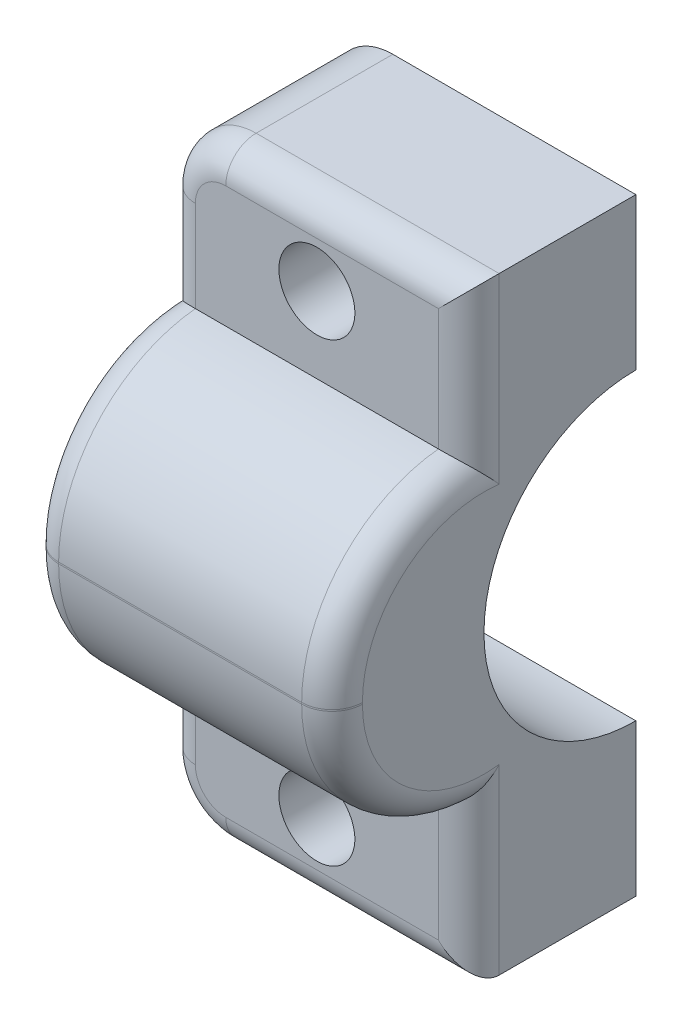
SolidWorks part; units mm, degrees
ref_plane "Front Plane" through (0, 0, 0) normal (0, 0, 1) x (1, 0, 0)
ref_plane "Top Plane" through (0, 0, 0) normal (0, 1, 0) x (1, 0, 0)
ref_plane "Right Plane" through (0, 0, 0) normal (1, 0, 0) x (0, 0, -1)
sketch "Sketch3" plane through (0, 0, 0) normal (0, 0, 1) x (1, 0, 0)
  line L0 (-22, -21.5) -> (-65, -21.5) construction
  line L1 (-65, -43) -> (65, -43) construction
  line L2 (-65, -43) -> (-65, 43) construction
  line L3 (-65, 43) -> (65, 43) construction
  line L4 (65, -43) -> (65, 43) construction
  line L5 (-65, -43) -> (65, 43) construction
  line L6 (-65, 43) -> (65, -43) construction
  line L7 (-65, -43) -> (-22, -43) construction
  line L8 (-65, -43) -> (-65, 0) construction
  line L9 (-65, 0) -> (-22, 0) construction
  line L10 (-22, -43) -> (-22, 0) construction
  circle A0 centre (-25, -3) radius 2.75
  circle A1 centre (-62, -3) radius 2.75
  circle A2 centre (-25, -40) radius 2.75
  circle A3 centre (-62, -40) radius 2.75
  point P0 (0, 0)
  dimension "D5" = 3
  dimension "D6" = 37
  dimension "D1" = 130
  dimension "D2" = 86
  dimension "D3" = 43
  dimension "D4" = 43
  dimension "D7" = 3
  dimension "D8" = 3
  dimension "D9" = 3
  dimension "D10" = 3
extrude "Boss-Extrude1" add sketch "Sketch3" along normal blind 6
sketch "Sketch4" plane through (0, 0, 0) normal (0, 0, 1) x (1, 0, 0)
  line L1 (-22, -43) -> (-65, -43)
  line L2 (-22, -43) -> (-22, 43)
  line L3 (-22, 43) -> (-65, 43)
  line L4 (-65, -43) -> (-65, 43)
extrude "Boss-Extrude2" add sketch "Sketch4" against normal blind 2.5
mirror "Mirror4" about plane through (0, 0, 0) normal (0, 1, 0) of "Boss-Extrude1"
sketch "Sketch5" plane through (0, 0, 6) normal (0, 0, 1) x (1, 0, 0)
  circle A0 centre (-25, 40) radius 2.75
extrude "Boss-Extrude3" add sketch "Sketch5" along normal blind 10
pattern_linear "LPattern1" count 2 spacing 37 along (-1, 0, 0) of "Boss-Extrude3"
pattern_linear "LPattern2" count 2 spacing 37 along (0, -1, 0) of "LPattern1"
sketch "Sketch6" plane through (0, 0, 0) normal (0, 0, 1) x (1, 0, 0)
  line L1 (-22, -43) -> (65, -43)
  line L2 (-22, -43) -> (-22, 43)
  line L3 (-22, 43) -> (65, 43)
  line L4 (65, -43) -> (65, 43)
extrude "Boss-Extrude4" add sketch "Sketch6" against normal blind 2.5
sketch "Sketch7" plane through (0, 0, 0) normal (0, 0, 1) x (1, 0, 0)
  line L0 (-22, -32.544) -> (-6, -32.544) construction
  line L1 (-22, -43) -> (-22, 0) construction
  line L2 (0, 0) -> (0, -43) construction
  line L3 (-65, -43) -> (65, -43) construction
  line L4 (0, -43) -> (-6, -32.544) construction
  line L5 (-6, -32.544) -> (0, -32.544) construction
  dimension "D1" = 16
  dimension "D2" = 6
ref_plane "Plane1" through (-6, 0, 0) normal (1, 0, 0) x (0, 0, -1)
sketch "Sketch11" plane through (-6, 0, 0) normal (1, 0, 0) x (0, 0, -1)
  line L0 (0, -43) -> (-40, -43)
  line L1 (-40, -43) -> (-40, -39)
  line L2 (0, -43) -> (0, -18)
  line L3 (0, -43) -> (0, 43) construction
  line L4 (-40, -39) -> (0, -18)
  dimension "D1" = 40
extrude "Boss-Extrude5" add sketch "Sketch11" along normal blind 2 and the other way blind 2
sketch "Sketch12" plane through (-8, 0, 0) normal (-1, 0, 0) x (0, 0, 1)
  line L0 (0, -43) -> (0, -36) construction
  line L1 (40, -43) -> (0, -43) construction
  line L2 (0, 43) -> (0, -43) construction
  line L3 (6, -37.25) -> (6, -36) construction
  line L8 (6, -42.75) -> (6, -37.25) construction
  line L9 (6, -37.25) -> (0, -37.25) construction
  line L10 (6, -36) -> (0, -36) construction
  line L12 (6, -36) -> (10, -36)
  line L13 (6, -36) -> (6, -28)
  line L14 (6, -28) -> (10, -28)
  line L15 (10, -36) -> (10, -28)
  dimension "D1" = 7
  dimension "D2" = 8
  dimension "D3" = 4
sketch "Sketch13" plane through (0, 0, 0) normal (0, 0, 1) x (1, 0, 0)
  line L0 (-22.25, -40) -> (-8, -40) construction
  line L1 (-8, -43) -> (-8, -36) construction
  circle A0 centre (-25, -40) radius 2.75 construction
  circle A1 centre (-25, -40) radius 2.75 construction
  dimension "D1" = 14.25
extrude "Cut-Extrude1" cut sketch "Sketch12" against normal blind 4
sketch "Sketch14" plane through (0, -43, 0) normal (0, -1, 0) x (1, 0, 0)
  line L0 (-6, -23.375) -> (-6, 23.375) construction
  line L1 (-8, 40) -> (-4, 40) construction
  line L2 (-6, 37) -> (-6, 13.6) construction
  circle A0 centre (-6, 37) radius 0.85
  circle A2 centre (-6, 13.6) radius 0.85
  dimension "D1" = 3
  dimension "D2" = 23.4
extrude "Cut-Extrude2" cut sketch "Sketch14" against normal blind 4.5
pattern_linear "LPattern3" count 2 spacing 46.5 along (1, 0, 0) of "Boss-Extrude5", "Cut-Extrude2"
sketch "Sketch16" plane through (0, -43, 0) normal (0, -1, 0) x (1, 0, 0)
  line L0 (40.5, 13.6) -> (40.5, -2.5)
  line L1 (-65, -2.5) -> (65, -2.5) construction
sketch "Sketch17" plane through (0, 0, 0) normal (0, 0, 1) x (1, 0, 0)
  line L0 (42.5, -43) -> (42.5, -41) construction
  line L1 (42.5, -43) -> (42.5, -18) construction
  line L2 (61.9, -8.8) -> (63.9, -8.8) construction
  line L3 (42.5, -41) -> (61.9, -41) construction
  line L4 (42.5, -41) -> (42.5, 23.4) construction
  line L5 (42.5, 23.4) -> (61.9, 23.4) construction
  line L6 (61.9, -41) -> (61.9, 23.4) construction
  line L7 (52.2, 23.4) -> (52.2, 25.4) construction
  line L8 (42.5, -8.8) -> (40.5, -8.8) construction
  line L9 (42.5, -41) -> (42.5, -43)
  line L10 (42.5, -43) -> (63.9, -43)
  line L11 (42.5, -43) -> (65, -43) construction
  line L12 (63.9, -43) -> (63.9, 25.4)
  line L13 (63.9, 25.4) -> (40.5, 25.4)
  line L14 (40.5, 25.4) -> (40.5, -18)
  line L15 (38.5, -18) -> (42.5, -18) construction
  line L16 (40.5, -18) -> (42.5, -18)
  line L17 (42.5, -18) -> (42.5, 23.4)
  line L18 (42.5, 23.4) -> (61.9, 23.4)
  line L19 (61.9, 23.4) -> (61.9, -41)
  line L20 (61.9, -41) -> (42.5, -41)
  dimension "D1" = 19.4
  dimension "D2" = 64.4
extrude "Boss-Extrude6" add sketch "Sketch17" along normal blind 35
sketch "Sketch18" plane through (0, -18, 0) normal (0, -1, 0) x (1, 0, 0)
  line L1 (42.5, 35) -> (40.5, 35)
  line L2 (42.5, 35) -> (42.5, 0)
  line L3 (42.5, 0) -> (40.5, 0)
  line L4 (40.5, 35) -> (40.5, 0)
extrude "Boss-Extrude7" add sketch "Sketch18" along normal blind 18.5
sketch "Sketch19" plane through (0, 0, 0) normal (0, 0, 1) x (1, 0, 0)
  line L1 (0, 0) -> (32.48, 0)
  line L2 (0, 0) -> (0, 17.04)
  line L3 (0, 17.04) -> (32.48, 17.04)
  line L4 (32.48, 0) -> (32.48, 17.04)
  dimension "D1" = 32.48
  dimension "D2" = 17.04
extrude "Boss-Extrude8" add sketch "Sketch19" along normal blind 10
sketch "Sketch20" plane through (0, 0, 10) normal (0, 0, 1) x (1, 0, 0)
  line L0 (0, 17.04) -> (0, 0) construction
  line L1 (2, 2) -> (10.16, 2)
  line L2 (2, 2) -> (2, 15.04)
  line L3 (2, 15.04) -> (10.16, 15.04)
  line L4 (10.16, 2) -> (10.16, 15.04)
  line L5 (0, 0) -> (32.48, 0) construction
  line L6 (32.48, 17.04) -> (0, 17.04) construction
  line L7 (32.48, 0) -> (32.48, 17.04) construction
  line L8 (12.16, 15.04) -> (20.32, 15.04)
  line L9 (12.16, 15.04) -> (12.16, 2)
  line L10 (12.16, 2) -> (20.32, 2)
  line L11 (20.32, 15.04) -> (20.32, 2)
  line L12 (22.32, 15.04) -> (30.48, 15.04)
  line L13 (22.32, 15.04) -> (22.32, 2)
  line L14 (22.32, 2) -> (30.48, 2)
  line L15 (30.48, 15.04) -> (30.48, 2)
  line L16 (0, 17.04) -> (32.48, 17.04) construction
  dimension "D1" = 2
  dimension "D2" = 2
  dimension "D3" = 2
  dimension "D4" = 2
  dimension "D5" = 2
  dimension "D6" = 2
  dimension "D7" = 8.16
  dimension "D8" = 8.16
  dimension "D9" = 8.16
  dimension "D10" = 13.04
  dimension "D11" = 13.04
  dimension "D12" = 13.04
  dimension "D13" = 2
extrude "Cut-Extrude3" cut sketch "Sketch20" against normal blind 10
sketch "Sketch21" plane through (0, 0, 0) normal (0, 0, 1) x (1, 0, 0)
  line L0 (65, -43) -> (65, 43) construction
  line L1 (63.9, -43) -> (65, -43)
  line L2 (63.9, -43) -> (63.9, 43)
  line L3 (63.9, 43) -> (65, 43)
  line L4 (65, -43) -> (65, 43)
extrude "Cut-Extrude4" cut sketch "Sketch21" against normal blind 10
fillet "Fillet2" radius 2 4 edges at (-65, 43, -1.25) (-65, -43, -1.25) (63.9, 25.4, 17.5) (63.9, -43, 16.25)
fillet "Fillet4" radius 20 1 edges at (63.9, 43, -1.25)
sketch "Sketch23" plane through (0, 0, -2.5) normal (0, 0, -1) x (-1, 0, 0)
  line L0 (0, 0) -> (65, 0) construction
  line L1 (65, 41) -> (65, -41) construction
  line L2 (65, 0) -> (105, 0) construction
  line L3 (105, 10) -> (105, -10) construction
  line L4 (105, -10) -> (105, -16) construction
  line L5 (65, 41) -> (65, -41) construction
  line L6 (95.4802, -10) -> (105, -10)
  line L7 (105, -10) -> (110, -10)
  line L8 (110, -10) -> (110, 10)
  line L9 (95.4802, 10) -> (105, 10)
  line L10 (65, -41) -> (65, 41)
  line L11 (105, 10) -> (110, 10)
  spline S0 degree 2 poles (95.4802, -10) (68.263, -8.8623) (65, -41) knots 0 0 0 1 1 1
  spline S1 degree 2 poles (95.4802, 10) (68.263, 8.8623) (65, 41) knots 0 0 0 1 1 1
  point P9 (105, 0)
  point P18 (110, 0)
  dimension "D1" = 20
extrude "Boss-Extrude9" add sketch "Sketch23" against normal blind 2.5
sketch "Sketch24" plane through (0, 0, 0) normal (0, 0, 1) x (1, 0, 0)
  line L0 (-95.4802, -10) -> (-105, -10) construction
  line L1 (-110, 10) -> (-100, 10)
  line L2 (-110, 10) -> (-110, -10)
  line L3 (-110, -10) -> (-100, -10)
  line L4 (-100, 10) -> (-100, -10)
  line L5 (-105, 3.4723) -> (-65, 3.4723) construction
  line L6 (-105, 10) -> (-105, -10) construction
  line L7 (-65, -41) -> (-65, 41) construction
  dimension "D1" = 10
extrude "Boss-Extrude10" add sketch "Sketch24" along normal blind 30
sketch "Sketch25" plane through (-110, 0, 0) normal (-1, 0, 0) x (0, 0, 1)
  line L0 (30, 10) -> (-2.5, 10) construction
  line L3 (30, 10) -> (30, -10) construction
  line L4 (20, 5) -> (20, 10) construction
  circle A0 centre (20, 0) radius 5
  dimension "D1" = 10
  dimension "D2" = 10
extrude "Cut-Extrude6" cut sketch "Sketch25" against normal blind 30
fillet "Fillet6" radius 10 1 edges at (-100, 0, 0)
fillet "Fillet8" radius 2 2 edges at (-110, 10, 13.75) (-110, -10, 13.75)
sketch "Sketch27" plane through (0, 0, -2.5) normal (0, 0, -1) x (-1, 0, 0)
  line L0 (110, 5) -> (110, 10) construction
  line L1 (110, 10) -> (90, 10)
  line L2 (110, 10) -> (110, -10.1307)
  line L3 (110, -10.1307) -> (90, -10.1307)
  line L4 (90, 10) -> (90, -10.1307)
extrude "Cut-Extrude7" cut sketch "Sketch27" against normal blind 22.5
sketch "Sketch28" plane through (-90, 0, 0) normal (-1, 0, 0) x (0, 0, 1)
  line L1 (-12.2204, 55.5192) -> (66.9065, 55.5192)
  line L2 (-12.2204, 55.5192) -> (-12.2204, -56.8134)
  line L3 (-12.2204, -56.8134) -> (66.9065, -56.8134)
  line L4 (66.9065, 55.5192) -> (66.9065, -56.8134)
extrude "Cut-Extrude10" cut sketch "Sketch28" against normal blind 210.5 and the other way blind 7.5
sketch "Sketch29" plane through (0, 0, 20) normal (0, 0, -1) x (-1, 0, 0)
  line L0 (105, 5) -> (105, 10) construction
  line L1 (110, 5) -> (100, 5) construction
  line L2 (108, 10) -> (100, 10) construction
  line L3 (100, 7.5) -> (110, 7.5) construction
  line L4 (100, 5) -> (100, 10) construction
  line L5 (110, 5) -> (110, 10) construction
  circle A0 centre (105, 7.5) radius 1.25
extrude "Cut-Extrude11" cut sketch "Sketch29" against normal blind 19.5
sketch "Sketch30" plane through (0, 0, 30) normal (0, 0, 1) x (1, 0, 0)
  line L1 (-110, 5) -> (-100, 5)
  line L2 (-110, 5) -> (-110, 10)
  line L3 (-110, 10) -> (-100, 10)
  line L4 (-100, 5) -> (-100, 10)
extrude "Cut-Extrude12" cut sketch "Sketch30" against normal blind 4.5
sketch "Sketch31" plane through (0, 0, 30) normal (0, 0, 1) x (1, 0, 0)
  line L0 (-110, 0) -> (-100, 0) construction
  line L1 (-110, 5) -> (-110, -5) construction
  line L2 (-100, -10) -> (-100, 5) construction
fillet "Fillet9" radius 5 1 edges at (-105, 5, 30)
mirror "Mirror5" about plane through (0, 0, 0) normal (0, 1, 0) of "Cut-Extrude11", "Cut-Extrude12", "Fillet9"
fillet "Fillet11" radius 1 14 edges at (-100, -7.5, 25.5) (-100, 3.3792, 28.7081) (-100, 0, 30) (-110, 3.3792, 28.7081) (-110, 0, 30) (-104, 10, 25.5) (-109.4142, 9.4142, 25.5) (-110, -6.5, 25.5) (-104, -10, 25.5) (-100, -3.3792, 28.7081) (-110, -3.3792, 28.7081) (-100, 7.5, 25.5) (-110, 6.5, 25.5) (-109.4142, -9.4142, 25.5)
